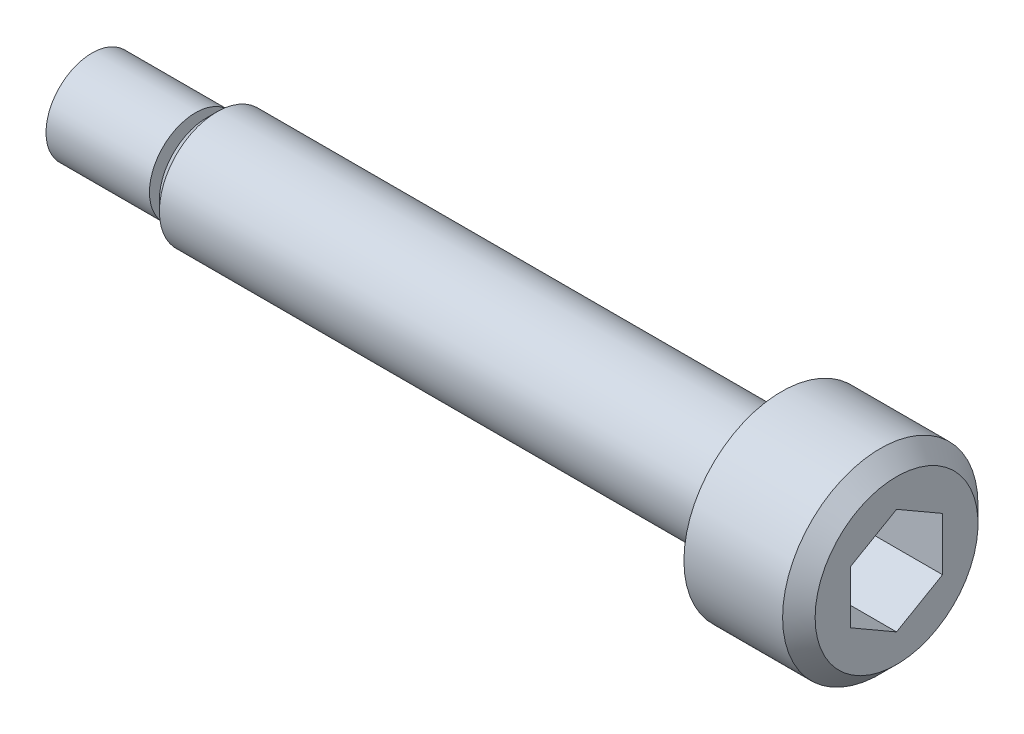
SolidWorks part; units mm, degrees
ref_plane "前视基准面" through (0, 0, 0) normal (0, 0, 1) x (1, 0, 0)
ref_plane "上视基准面" through (0, 0, 0) normal (0, 1, 0) x (1, 0, 0)
ref_plane "右视基准面" through (0, 0, 0) normal (1, 0, 0) x (0, 0, -1)
sketch "草图1" plane through (0, 0, 0) normal (0, 0, 1) x (1, 0, 0)
  line L0 (-5, 0) -> (-5, 2)
  line L1 (-5, 2) -> (-0.5, 2)
  line L2 (-0.5, 2) -> (-0.5, 1.3)
  line L3 (-0.5, 1.3) -> (0, 1.3)
  line L4 (0, 1.3) -> (0, 2.067)
  line L5 (0, 2.067) -> (0.433, 2.5)
  line L6 (0.433, 2.5) -> (25, 2.5)
  line L7 (25, 2.5) -> (25, 4.25)
  line L8 (25, 4.25) -> (29.2929, 4.25)
  line L9 (29.2929, 4.25) -> (30, 3.5429)
  line L10 (30, 3.5429) -> (30, 0)
  line L11 (30, 0) -> (-5, 0)
  line L12 (30, 0) -> (-5, 0) construction
revolve "旋转1" add sketch "草图1" angle 360 about L12 reverse direction yes
cosmetic thread "装饰螺纹线1" parameters "D1"=23.75, "D2"=4.134
sketch "草图2" plane through (0, 0, 0) normal (0, 0, 1) x (1, 0, 0)
  line L0 (24.8453, 0) -> (26, 2)
  line L1 (26, 2) -> (30, 2)
  line L2 (30, 2) -> (30, 0)
  line L3 (30, 0) -> (24.8453, 0)
  line L4 (30, 0) -> (24.8453, 0) construction
revolve "切除-旋转1" cut sketch "草图2" angle 360 about L4 reverse direction yes
ref_plane "基准面1" through (30, 0, 0) normal (1, 0, 0) x (0, 0, -1)
sketch "草图3" plane through (30, 0, 0) normal (1, 0, 0) x (0, 0, -1)
  line L0 (-2, 1.1547) -> (-2, -1.1547)
  line L1 (-2, -1.1547) -> (0, -2.3094)
  line L2 (0, -2.3094) -> (2, -1.1547)
  line L3 (2, -1.1547) -> (2, 1.1547)
  line L4 (2, 1.1547) -> (0, 2.3094)
  line L5 (0, 2.3094) -> (-2, 1.1547)
extrude "切除-拉伸1" cut sketch "草图3" against normal blind 4
ref_plane "基准面2" through (12.5, 0, 0) normal (1, 0, 0) x (0, 0, -1)
ref_plane "uuscbb_n XY" through (12.5, 0, 0) normal (1, 0, 0) x (0, 0, -1)
ref_plane "uuscbb_n XZ" through (0, 0, 0) normal (0, -1, 0) x (1, 0, 0)
ref_plane "uuscbb_n YZ" through (0, 0, 0) normal (0, 0, -1) x (-1, 0, 0)
ref_axis "uuscbb_n X" through (12.5, 0, 80.9) along (0, 0, -1)
ref_axis "uuscbb_n Y" through (12.5, -50, 0) along (0, 1, 0)
ref_axis "uuscbb_n Z" through (80.9, 0, 0) along (-1, 0, 0)
sketch3d "uuscbb_n"
  point P0 (12.5, 0, 0)
